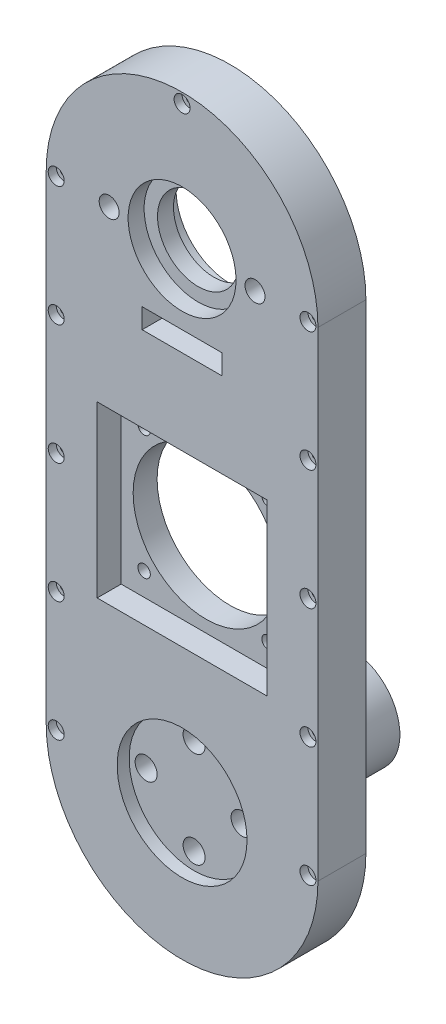
SolidWorks part; units mm, degrees
ref_plane "Front Plane" through (0, 0, 0) normal (0, 0, 1) x (1, 0, 0)
ref_plane "Top Plane" through (0, 0, 0) normal (0, 1, 0) x (1, 0, 0)
ref_plane "Right Plane" through (0, 0, 0) normal (1, 0, 0) x (0, 0, -1)
sketch "Sketch1" plane through (0, 0, 0) normal (0, 0, 1) x (1, 0, 0)
  line L2 (-34, -60) -> (-34, 60)
  line L4 (34, -60) -> (34, 60)
  line L5 (-34, -60) -> (34, 60) construction
  line L6 (-34, 60) -> (34, -60) construction
  arc A0 (34, -60) -> (-34, -60) centre (0, -60) cw
  arc A1 (-34, 60) -> (34, 60) centre (0, 60) cw
  point P0 (0, 0)
  dimension "D1" = 120
  dimension "D2" = 68
extrude "Boss-Extrude1" add sketch "Sketch1" along normal blind 12
sketch "Sketch2" plane through (0, 0, 12) normal (0, 0, 1) x (1, 0, 0)
  arc A0 (-34, -60) -> (34, -60) centre (0, -60) ccw construction
  arc A1 (-34, -60) -> (34, -60) centre (0, -60) ccw construction
  circle A2 centre (0, -60) radius 16.25
  dimension "D1" = 32.5
extrude "Cut-Extrude1" cut sketch "Sketch2" against normal blind 3
sketch "Sketch3" plane through (0, 0, 9) normal (0, 0, 1) x (1, 0, 0)
  circle A0 centre (0, -48) radius 2.75
  circle A1 centre (0, -60) radius 16.25
  circle A2 centre (0, -60) radius 16.25 construction
  circle A3 centre (12, -60) radius 2.75
  circle A4 centre (0, -72) radius 2.75
  circle A5 centre (-12, -60) radius 2.75
  point P14 (0, -60)
  dimension "D2" = 5.5
  dimension "D3" = 12
  dimension "D1" = 0
  dimension "D4" = 4
extrude "Cut-Extrude2" cut sketch "Sketch3" against normal blind 5
sketch "Sketch4" plane through (0, 0, 0) normal (0, 0, -1) x (-1, 0, 0)
  arc A0 (-34, -60) -> (34, -60) centre (0, -60) ccw construction
  arc A1 (-34, -60) -> (34, -60) centre (0, -60) ccw construction
  circle A2 centre (0, -60) radius 12.5
  dimension "D1" = 25
extrude "Boss-Extrude2" add sketch "Sketch4" along normal blind 30
sketch "Sketch12" plane through (0, 0, 12) normal (0, 0, 1) x (1, 0, 0)
  line L0 (0, 0) -> (0, -5) construction
  line L1 (-15.5, -20.5) -> (15.5, -20.5) construction
  line L2 (-15.5, -20.5) -> (-15.5, 10.5) construction
  line L3 (-15.5, 10.5) -> (15.5, 10.5) construction
  line L4 (15.5, -20.5) -> (15.5, 10.5) construction
  line L5 (-15.5, -20.5) -> (15.5, 10.5) construction
  line L6 (-15.5, 10.5) -> (15.5, -20.5) construction
  circle A8 centre (-15.5, 10.5) radius 1.55
  circle A9 centre (15.5, 10.5) radius 1.55
  circle A10 centre (15.5, -20.5) radius 1.55
  circle A11 centre (-15.5, -20.5) radius 1.55
  circle A12 centre (0, -5) radius 18.25
  point P0 (0, -5)
  point P18 (0, -5)
  dimension "D3" = 3.1
  dimension "D5" = 36.5
  dimension "D1" = 31
  dimension "D2" = 5
  dimension "D4" = 4
extrude "Cut-Extrude9" cut sketch "Sketch12" against normal up to next
sketch "Sketch13" plane through (0, 0, 0) normal (0, 0, -1) x (-1, 0, 0)
  line L0 (0, 0) -> (0, -5) construction
  line L1 (-15.5, -20.5) -> (15.5, -20.5) construction
  line L2 (-15.5, -20.5) -> (-15.5, 10.5) construction
  line L3 (-15.5, 10.5) -> (15.5, 10.5) construction
  line L4 (15.5, -20.5) -> (15.5, 10.5) construction
  line L5 (-15.5, -20.5) -> (15.5, 10.5) construction
  line L6 (-15.5, 10.5) -> (15.5, -20.5) construction
  circle A8 centre (15.5, 10.5) radius 3
  circle A9 centre (15.5, -20.5) radius 3
  circle A10 centre (-15.5, -20.5) radius 3
  circle A11 centre (-15.5, 10.5) radius 3
  circle A12 centre (0, -5) radius 18.25 construction
  circle A13 centre (0, -5) radius 18.25 construction
  point P0 (0, -5)
  point P17 (0, -5)
  dimension "D2" = 5
  dimension "D3" = 6
  dimension "D1" = 31
  dimension "D4" = 4
extrude "Cut-Extrude10" cut sketch "Sketch13" against normal blind 3
sketch "Sketch14" plane through (0, 0, 12) normal (0, 0, 1) x (1, 0, 0)
  arc A0 (34, 60) -> (-34, 60) centre (0, 60) ccw construction
  arc A1 (34, 60) -> (-34, 60) centre (0, 60) ccw construction
  circle A2 centre (0, 60) radius 10.15
  dimension "D1" = 20.3
extrude "Cut-Extrude11" cut sketch "Sketch14" against normal up to next
sketch "Sketch15" plane through (0, 0, 12) normal (0, 0, 1) x (1, 0, 0)
  circle A0 centre (0, 60) radius 10.15 construction
  circle A1 centre (0, 60) radius 10.15 construction
  circle A2 centre (0, 60) radius 13.5
  dimension "D1" = 27
extrude "Cut-Extrude12" cut sketch "Sketch15" against normal blind 4
ref_plane "Plane1" through (0, 0, 6) normal (0, 0, 1) x (1, 0, 0)
mirror "Mirror1" about plane through (0, 0, 6) normal (0, 0, 1) of "Cut-Extrude12"
sketch "Sketch19" plane through (0, 0, 12) normal (0, 0, 1) x (1, 0, 0)
  line L0 (31.5, 60) -> (-31.5, 60) construction
  line L1 (0, 60) -> (0, 0) construction
  line L2 (-31.5, 60) -> (-31.5, -58.8117) construction
  line L3 (31.5, 60) -> (31.5, -58.8117) construction
  line L4 (0, 60) -> (0, 91.5) construction
  arc A0 (31.5, 60) -> (-31.5, 60) centre (0, 60) ccw construction
  circle A1 centre (0, 91.5) radius 1
  circle A2 centre (-31.5, 60) radius 1
  circle A3 centre (31.5, 60) radius 1
  circle A4 centre (31.5, 30) radius 1
  circle A5 centre (31.5, 0) radius 1
  circle A6 centre (31.5, -30) radius 1
  circle A9 centre (-31.5, 30) radius 1
  circle A10 centre (-31.5, 0) radius 1
  circle A11 centre (-31.5, -30) radius 1
  point P6 (0, 60)
  dimension "D1" = 63
  dimension "D2" = 2
  dimension "D3" = 2
  dimension "D4" = 2
  dimension "D5" = 4
extrude "Cut-Extrude17" cut sketch "Sketch19" against normal up to next
sketch "Sketch20" plane through (0, 0, 0) normal (0, 0, 1) x (1, 0, 0)
  line L0 (31.5, 60) -> (-31.5, 60) construction
  line L1 (0, 0) -> (0, 60) construction
  line L2 (-31.5, 60) -> (-31.5, -60.6771) construction
  line L3 (31.5, 60) -> (31.5, -60.6771) construction
  line L4 (0, 60) -> (0, 91.5) construction
  arc A0 (31.5, 60) -> (-31.5, 60) centre (0, 60) ccw construction
  circle A1 centre (0, 91.5) radius 2
  circle A2 centre (-31.5, 60) radius 2
  circle A3 centre (31.5, 60) radius 2
  circle A4 centre (31.5, 30) radius 2
  circle A5 centre (31.5, 0) radius 2
  circle A6 centre (31.5, -30) radius 2
  circle A7 centre (31.5, -60) radius 2
  circle A9 centre (-31.5, 30) radius 2
  circle A10 centre (-31.5, 0) radius 2
  circle A11 centre (-31.5, -30) radius 2
  circle A12 centre (-31.5, -60) radius 2
  circle A13 centre (0, 60) radius 13.5 construction
  circle A14 centre (0, 60) radius 13.5 construction
  dimension "D1" = 63
  dimension "D2" = 4
  dimension "D3" = 4
  dimension "D4" = 2
  dimension "D5" = 5
  dimension "D6" = 60
extrude "Cut-Extrude18" cut sketch "Sketch20" against normal blind 2 from surface starting at face at (1, 91.5, 12)
sketch "Sketch21" plane through (0, 0, 12) normal (0, 0, 1) x (1, 0, 0)
  line L0 (18.25, 60) -> (-18.25, 60) construction
  circle A0 centre (0, 60) radius 13.5 construction
  circle A1 centre (0, 60) radius 13.5 construction
  circle A2 centre (-18.25, 60) radius 2.5
  circle A3 centre (18.25, 60) radius 2.5
  point P6 (0, 60)
  dimension "D2" = 5
  dimension "D3" = 5
  dimension "D1" = 36.5
extrude "Cut-Extrude19" cut sketch "Sketch21" against normal up to next
sketch "Sketch22" plane through (0, 0, 12) normal (0, 0, 1) x (1, 0, 0)
  line L1 (-21.25, -26.25) -> (21.25, -26.25)
  line L2 (-21.25, -26.25) -> (-21.25, 16.25)
  line L3 (-21.25, 16.25) -> (21.25, 16.25)
  line L4 (21.25, -26.25) -> (21.25, 16.25)
  line L5 (-21.25, -26.25) -> (21.25, 16.25) construction
  line L6 (-21.25, 16.25) -> (21.25, -26.25) construction
  circle A0 centre (0, -5) radius 18.25 construction
  circle A1 centre (0, -5) radius 18.25 construction
  dimension "D1" = 42.5
extrude "Cut-Extrude20" cut sketch "Sketch22" against normal blind 6
sketch "Sketch23" plane through (0, 0, 0) normal (0, 0, -1) x (-1, 0, 0)
  line L0 (0, 0) -> (0, 40) construction
  line L6 (-10, 37.5) -> (10, 37.5)
  line L7 (-10, 37.5) -> (-10, 42.5)
  line L8 (-10, 42.5) -> (10, 42.5)
  line L9 (10, 37.5) -> (10, 42.5)
  line L10 (-10, 37.5) -> (10, 42.5) construction
  line L11 (-10, 42.5) -> (10, 37.5) construction
  dimension "D1" = 5
  dimension "D2" = 20
  dimension "D3" = 40
extrude "Cut-Extrude21" cut sketch "Sketch23" against normal up to next
